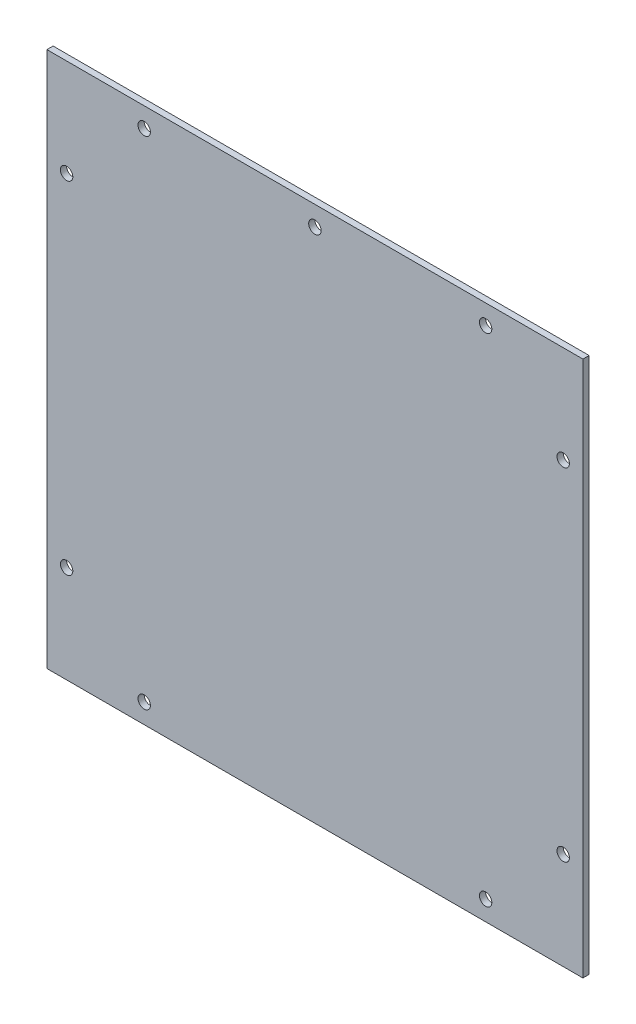
SolidWorks part; units mm, degrees
material "5052-O"
ref_plane "Front Plane" through (0, 0, 0) normal (0, 0, 1) x (1, 0, 0)
ref_plane "Top Plane" through (0, 0, 0) normal (0, 1, 0) x (1, 0, 0)
ref_plane "Right Plane" through (0, 0, 0) normal (1, 0, 0) x (0, 0, -1)
sketch "Sketch2" plane through (0, 0, 0) normal (0, 0, 1) x (1, 0, 0)
  line L1 (-172.7, 172.7) -> (172.7, 172.7)
  line L2 (-172.7, 172.7) -> (-172.7, -172.7)
  line L3 (-172.7, -172.7) -> (172.7, -172.7)
  line L4 (172.7, 172.7) -> (172.7, -172.7)
  circle A1 centre (-110, 160) radius 4
  circle A2 centre (-160, 110) radius 4
  circle A3 centre (-160, -110) radius 4
  circle A4 centre (-110, -160) radius 4
  circle A5 centre (110, -160) radius 4
  circle A6 centre (160, -110) radius 4
  circle A7 centre (160, 110) radius 4
  circle A8 centre (110, 160) radius 4
  circle A9 centre (0, 160) radius 4
  dimension "D5" = 8
  dimension "D6" = 8
  dimension "D7" = 8
  dimension "D8" = 8
  dimension "D9" = 8
  dimension "D10" = 8
  dimension "D11" = 8
  dimension "D12" = 8
  dimension "D13" = 8
  dimension "D1" = 345.4
  dimension "D2" = 345.4
  dimension "D3" = 172.7
  dimension "D4" = 172.7
extrude "Boss-Extrude2" add sketch "Sketch2" along normal blind 4
